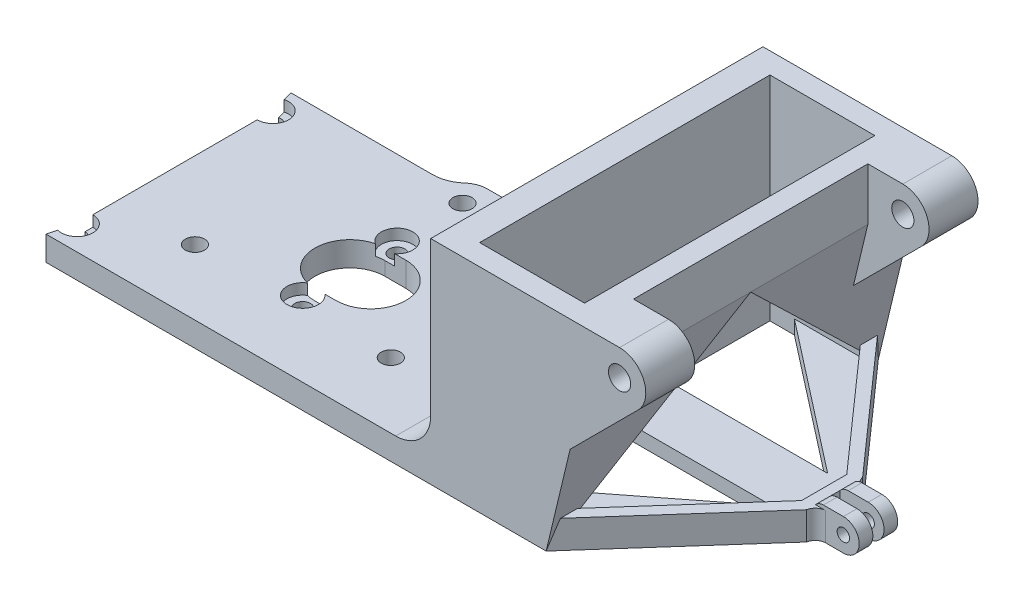
SolidWorks part; units mm, degrees
ref_plane "Front Plane" through (0, 0, 0) normal (0, 0, 1) x (1, 0, 0)
ref_plane "Top Plane" through (0, 0, 0) normal (0, 1, 0) x (1, 0, 0)
ref_plane "Right Plane" through (0, 0, 0) normal (1, 0, 0) x (0, 0, -1)
sketch "Sketch1" plane through (0, 0, 0) normal (0, 1, 0) x (1, 0, 0)
  line L1 (-35, 60) -> (80, 60)
  line L2 (-35, 60) -> (-35, -35)
  line L3 (-35, -35) -> (80, -35)
  line L4 (80, 60) -> (80, -35)
  point P0 (0, 0)
  dimension "D1" = 115
  dimension "D2" = 95
  dimension "D3" = 35
  dimension "D4" = 35
extrude "Extrude1" add sketch "Sketch1" along normal blind 7
sketch "Sketch2" plane through (0, 0, 0) normal (0, 1, 0) x (1, 0, 0)
  line L0 (-28.109, -30.4503) -> (-28.109, 28) construction
  line L1 (-35, 60) -> (-35, -35) construction
  line L2 (-47.7977, 0) -> (51.3963, 0) construction
  line L3 (21.891, -18.2702) -> (21.891, 18.8238) construction
  line L4 (5, -25.5364) -> (5, 23.1606) construction
  line L5 (-13, -30.4503) -> (-13, 32.9416) construction
  line L6 (38.782, 10.2941) -> (38.782, -21.3756) construction
  line L7 (20.5161, -20) -> (37.327, -20) construction
  line L8 (21.891, -13.5) -> (-7.9984, -13.5) construction
  line L9 (21.891, 10) -> (27.891, 10)
  line L10 (21.891, -10) -> (27.891, -10)
  circle A0 centre (-6.109, -16.3) radius 2.75
  circle A1 centre (49.891, -16.3) radius 2.75
  circle A2 centre (-28.109, -28) radius 2.25
  circle A3 centre (-28.109, 28) radius 2.25
  circle A4 centre (21.891, 32.2) radius 2.75
  arc A5 (21.891, 10) -> (21.891, -10) centre (21.891, 0) ccw
  circle A6 centre (21.891, -13.5) radius 2.25
  circle A7 centre (21.891, 13.5) radius 2.25
  arc A8 (27.891, 10) -> (27.891, -10) centre (27.891, 0) cw
  dimension "D4" = 16.891
  dimension "D5" = 28
  dimension "D6" = 4.5
  dimension "D7" = 50
  dimension "D10" = 28
  dimension "D11" = 2.8
  dimension "D12" = 4.5
  dimension "D13" = 4.5
  dimension "D17" = 48.5
  dimension "D18" = 5.5
  dimension "D19" = 5.5
  dimension "D21" = 10
  dimension "D23" = 6
  dimension "D3" = 4.5
  dimension "D14" = 5.5
  dimension "D16" = 28
  dimension "D1" = 6.891
  dimension "D2" = 28
  dimension "D8" = 13.5
  dimension "D9" = 13.5
  dimension "D15" = 40
  dimension "D20" = 18
extrude "Extrude7" cut sketch "Sketch2" along normal blind 7
hole_wizard "CBORE for M4 Pan Head Machine Screw2" positions "3DSketch10" profile "Sketch14" counterbore size "M4" standard "Ansi Metric" end condition through all
sketch3d "3DSketch10"
  line L0 (-28.109, 7, -28) -> (-28.109, 0, -28) construction
  line L1 (21.891, 7, -13.5) -> (21.891, 0, -13.5) construction
  line L2 (21.891, 7, 13.5) -> (21.891, 0, 13.5) construction
  line L3 (-28.109, 7, 28) -> (-28.109, 0, 28) construction
  point P0 (-28.109, 7, -28)
  point P4 (21.891, 7, -13.5)
  point P8 (21.891, 7, 13.5)
  point P12 (-28.109, 7, 28)
sketch "Sketch14" plane through (-28.109, 7, -28) normal (1, 0, 0) x (0, 0, 1)
  line L0 (0, 0) -> (0, 7)
  line L1 (0, 7) -> (2.25, 7)
  line L3 (2.25, 7) -> (2.25, 3.1)
  line L4 (2.25, 3.1) -> (4.5, 3.1)
  line L5 (4.5, 3.1) -> (4.5, 0)
  line L7 (4.5, 0) -> (0, 0)
  line L11 (0, -6.35) -> (0, 107.95) construction
  dimension "Thru Hole Dia." = 4.5
  dimension "Thru Hole Depth" = 7
  dimension "C'Bore Dia." = 9
  dimension "C'Bore Depth" = 3.1
sketch "Sketch18" plane through (0, 7, 0) normal (0, 1, 0) x (1, 0, 0)
  line L0 (26.1303, 32.2) -> (16.7823, 32.2) construction
  line L1 (21.891, 39.3001) -> (21.891, 26.9019) construction
  line L2 (30, 39.3001) -> (21.891, 39.3001)
  line L4 (-30, -35) -> (-35, -35)
  line L5 (-35, 60) -> (-35, -35) construction
  line L6 (-35, 35) -> (-35, 60)
  line L7 (-35, 60) -> (80, 60)
  line L8 (80, 60) -> (80, 39.3001)
  line L9 (-28.109, 28) -> (-28.109, -28)
  line L10 (-28.109, -28) -> (-30, -35)
  line L11 (-35, -35) -> (80, -35) construction
  line L12 (-30, 35) -> (15.4327, 35)
  line L13 (-35, -35) -> (-35, 35)
  line L14 (-28.109, 28) -> (-30, 35)
  line L15 (35, 44.3001) -> (35, 60)
  arc A0 (21.891, 39.3001) -> (15.4327, 35) centre (21.891, 32.3001) ccw
  arc A1 (35, 44.3001) -> (30, 39.3001) centre (30, 44.3001) cw
  circle M1 centre (-28.109, 28) radius 4.5
  circle M4 centre (-28.109, -28) radius 4.5
  line M8 (-35, 60) -> (-35, -35)
  line M9 (-35, -35) -> (80, -35)
  dimension "D1" = 7
  dimension "D4" = 5
  dimension "D2" = 45
  dimension "D3" = 5
extrude "Extrude9" cut sketch "Sketch18" against normal through all contours A1 L15 L7 L10 L9 L14 L12 A0 L2 M8 M9 M4 M1 | L9 L14 M1 | L10 L9 M4 region at (-7.338, 7, -38.5155) region at (-30.1578, 7, -27.7281) region at (-30.1578, 7, 27.7281)
fillet "Fillet1" radius 10 2 edges at (35, 3.5, -60) (15.4327, 3.5, -35)
sketch "Sketch19" plane through (80, 0, 0) normal (1, 0, 0) x (0, 0, -1)
  line L0 (-35, 7) -> (-35, 0) construction
  line L1 (60, 0) -> (-35, 0)
  line L2 (60, 0) -> (60, 60.9)
  line L3 (60, 60.9) -> (-35, 60.9)
  line L4 (-35, 0) -> (-35, 60.9)
  dimension "D1" = 60.9
extrude "Boss-Extrude1" add sketch "Sketch19" along normal blind 8
sketch "Sketch20" plane through (0, 0, -60) normal (0, 0, -1) x (-1, 0, 0)
  line L0 (-88, 0) -> (-113, 0)
  line L1 (-113, 0) -> (-124, 45.9)
  line L2 (-124, 45.9) -> (-124, 60.9)
  line L3 (-124, 60.9) -> (-88, 60.9)
  line L10 (-88, 0) -> (-45, 0)
  line L11 (-45, 0) -> (-45, 7)
  line L12 (-45, 7) -> (-80, 7)
  line L13 (-80, 7) -> (-80, 60.9)
  line L14 (-80, 60.9) -> (-88, 60.9)
  line L15 (-88, 60.9) -> (-88, 0)
  line L16 (-88, 0) -> (-45, 0)
  line L17 (-45, 0) -> (-45, 7)
  line L18 (-45, 7) -> (-80, 7)
  line L19 (-80, 7) -> (-80, 60.9)
  line L20 (-80, 60.9) -> (-88, 60.9)
  dimension "D1" = 15
  dimension "D2" = 36
  dimension "D3" = 25
  dimension "D4" = 0
extrude "Boss-Extrude2" add sketch "Sketch20" against normal blind 6
sketch "Sketch21" plane through (0, 0, 35) normal (0, 0, 1) x (1, 0, 0)
  line L5 (88, 60.9) -> (88, 0)
  line L6 (88, 0) -> (113, 0)
  line L7 (113, 0) -> (124, 45.9)
  line L8 (124, 45.9) -> (124, 60.9)
  line L9 (124, 60.9) -> (88, 60.9)
  line L10 (88, 60.9) -> (88, 0)
  line L11 (88, 0) -> (113, 0)
  line L12 (113, 0) -> (124, 45.9)
  line L13 (124, 45.9) -> (124, 60.9)
  line L14 (124, 60.9) -> (88, 60.9)
  dimension "D1" = 0
extrude "Boss-Extrude3" add sketch "Sketch21" against normal blind 6
sketch "Sketch22" plane through (0, 0, -54) normal (0, 0, 1) x (1, 0, 0)
  line L0 (88, 60.9) -> (124, 60.9) construction
  line L1 (124, 45.9) -> (118, 45.9)
  line L2 (124, 45.9) -> (124, 60.9)
  line L3 (124, 60.9) -> (118, 60.9)
  line L4 (118, 45.9) -> (118, 60.9)
  dimension "D1" = 6
extrude "Boss-Extrude4" add sketch "Sketch22" along normal up to surface (83 mm away) up to face at (107.4, 33.54, 29)
sketch "Sketch23" plane through (106.8626, -25.6098, 0) normal (0.9725, -0.2331, 0) x (0, 0, -1)
  line L0 (54, 32.0346) -> (12.5, 73.5346)
  line L1 (54, 73.5346) -> (54, 26.3349) construction
  line L2 (-29, 73.5346) -> (54, 73.5346) construction
  line L3 (12.5, 73.5346) -> (-29, 32.0346)
  line L4 (-29, 26.3349) -> (-29, 73.5346) construction
  line L5 (-29, 26.3349) -> (-29, 73.5346)
  line L6 (-29, 73.5346) -> (54, 73.5346)
  line L7 (54, 73.5346) -> (54, 26.3349)
  line M4 (54, 73.5346) -> (54, 26.3349)
  dimension "D1" = 45
extrude "Boss-Extrude5" add sketch "Sketch23" against normal up to vertex (5.8348 mm away) contours L6 L0 M4 | L6 L5 L3 region at (120.7761, 32.4476, 15.1667) region at (120.7761, 32.4476, -40.1667) up to point (118, 45.9, 29)
sketch "Sketch25" plane through (0, 0, -60) normal (0, 0, -1) x (-1, 0, 0)
  line L0 (-124, 60.9) -> (-80, 60.9) construction
  line L1 (-124, 45.9) -> (-134, 45.9)
  line L2 (-124, 45.9) -> (-124, 60.9)
  line L3 (-124, 60.9) -> (-134, 60.9)
  line L4 (-139.3033, 48.0967) -> (-119.869, 28.6624)
  line L5 (-124, 45.9) -> (-113, 0) construction
  line L6 (-119.869, 28.6624) -> (-124, 45.9)
  line L7 (-113, 0) -> (-45, 0) construction
  arc A0 (-134, 60.9) -> (-134, 45.9) centre (-134, 53.4) ccw
  circle A1 centre (-134, 53.4) radius 3.175
  line M8 (-124, 60.9) -> (-124, 45.9)
  line M9 (-124, 45.9) -> (-113, 0)
  dimension "D2" = 6.35
  dimension "D1" = 10
  dimension "D3" = 45
extrude "Boss-Extrude6" add sketch "Sketch25" against normal blind 14 contours L3 A0 L1 A1 M8 | A0 L4 L1 M9 region at (127.0971, 40.2198, -60) region at (129, 46.1305, -60)
sketch "Sketch26" plane through (0, 0, 35) normal (0, 0, 1) x (1, 0, 0)
  line L4 (134, 60.9) -> (124, 60.9)
  line L5 (124, 60.9) -> (124, 45.9)
  line L6 (124, 45.9) -> (119.869, 28.6624)
  line L7 (119.869, 28.6624) -> (139.3033, 48.0967)
  line L8 (134, 60.9) -> (124, 60.9)
  line L9 (124, 60.9) -> (124, 45.9)
  line L10 (124, 45.9) -> (119.869, 28.6624)
  line L11 (119.869, 28.6624) -> (139.3033, 48.0967)
  circle A0 centre (134, 53.4) radius 3.175 construction
  arc A1 (139.3033, 48.0967) -> (134, 60.9) centre (134, 53.4) ccw
  arc A2 (139.3033, 48.0967) -> (134, 60.9) centre (134, 53.4) ccw
  circle A3 centre (134, 53.4) radius 3.175
  dimension "D1" = 0
extrude "Boss-Extrude7" add sketch "Sketch26" against normal blind 14
fillet "Fillet2" radius 10 1 edges at (80, 7, -12.5)
sketch "Sketch27" plane through (0, 0, 0) normal (0, -1, 0) x (1, 0, 0)
  line L0 (113, 29) -> (113, 35) construction
  line L1 (88, -4.5) -> (148, -4.5)
  line L2 (88, -4.5) -> (88, -20.5)
  line L3 (88, -20.5) -> (148, -20.5)
  line L4 (148, -4.5) -> (148, -20.5)
  line L5 (113, -54) -> (113, -60) construction
  line L6 (88, 29) -> (88, -54) construction
  line L7 (113, -60) -> (45, -60) construction
  line L8 (-30, 35) -> (113, 35) construction
  line L9 (113, 29) -> (113, 35)
  line L10 (113, -54) -> (113, -60)
  line L11 (88, 29) -> (88, -54)
  line L12 (113, -60) -> (45, -60)
  line L13 (-30, 35) -> (113, 35)
  line L14 (88, -12.5) -> (148, -12.5) construction
  line L15 (113, 35) -> (148, -4.5)
  line L16 (148, -20.5) -> (113, -60)
  line L17 (138, -20.5) -> (95, -54)
  line L18 (113, -54) -> (88, -54) construction
  line L19 (138, -4.5) -> (95, 29)
  line L20 (88, 29) -> (113, 29) construction
  line L21 (88, 29) -> (113, 29)
  line L22 (113, -54) -> (88, -54)
  point P16 (0, 0)
  line M17 (113, -60) -> (113, -54)
  line M18 (113, -54) -> (88, -54)
  line M19 (88, -54) -> (88, 29)
  line M20 (88, 29) -> (113, 29)
  line M21 (113, 29) -> (113, 35)
  dimension "D1" = 60
  dimension "D2" = 16
  dimension "D3" = 7
  dimension "D4" = 7
  dimension "D5" = 10
extrude "Boss-Extrude8" add sketch "Sketch27" against normal blind 4 contours L19 L1 L15 M21 M20 | L11 L14 L4 L1 | L3 L17 L16 M18 M17 | L14 L3 L4 M19 region at (118, 0, -8.5) region at (122.196, 0, 14.9406) region at (118, 0, -16.5) region at (122.196, 0, -39.9406)
sketch "Sketch28" plane through (0, 4, 0) normal (0, 1, 0) x (1, 0, 0)
  line L0 (148, 15.5819) -> (113.9586, 54)
  line L1 (148, 4.5) -> (148, 20.5) construction
  line L2 (113.9586, -29) -> (148, 9.4181)
  line L3 (145, 23.8857) -> (145, 1.1143)
  line L14 (113.9586, 58.9181) -> (113.9586, 54)
  line L15 (113.9586, 54) -> (95, 54)
  line L16 (95, 54) -> (138, 20.5)
  line L17 (138, 20.5) -> (88, 20.5)
  line L18 (88, 20.5) -> (88, 4.5)
  line L19 (88, 4.5) -> (138, 4.5)
  line L20 (138, 4.5) -> (95, -29)
  line L21 (95, -29) -> (113.9586, -29)
  line L22 (113.9586, -29) -> (113.9586, -33.9181)
  line L23 (113.9586, -33.9181) -> (148, 4.5)
  line L24 (148, 4.5) -> (148, 20.5)
  line L25 (148, 20.5) -> (113.9586, 58.9181)
  line L26 (113.9586, 58.9181) -> (113.9586, 54)
  line L27 (113.9586, 54) -> (95, 54)
  line L28 (95, 54) -> (138, 20.5)
  line L29 (138, 20.5) -> (88, 20.5)
  line L30 (88, 20.5) -> (88, 4.5)
  line L31 (88, 4.5) -> (138, 4.5)
  line L32 (138, 4.5) -> (95, -29)
  line L33 (95, -29) -> (113.9586, -29)
  line L34 (113.9586, -29) -> (113.9586, -33.9181)
  line L35 (113.9586, -33.9181) -> (148, 4.5)
  line L36 (148, 4.5) -> (148, 20.5)
  line L37 (148, 20.5) -> (113.9586, 58.9181)
  line M15 (113.9586, 58.9181) -> (113.9586, 54)
  line M23 (113.9586, -29) -> (113.9586, -33.9181)
  line M24 (113.9586, -33.9181) -> (148, 4.5)
  line M25 (148, 4.5) -> (148, 20.5)
  line M26 (148, 20.5) -> (113.9586, 58.9181)
  dimension "D2" = 3
  dimension "D1" = 0
extrude "Boss-Extrude9" add sketch "Sketch28" along normal blind 4 contours L0 M25 M26 M15 | L2 M23 M24 M25 | L3 L0 M26 M25 | L0 L3 L2 M25 | L2 L3 M24 M25 region at (146.3227, 4, -12.5) region at (146.5, 4, -19.7338) region at (129.4793, 4, -38.9429) region at (146.5, 4, -5.2662) region at (129.4793, 4, 13.9429)
ref_plane "Plane1" through (0, 0, -12.5) normal (0, 0, 1) x (1, 0, 0)
sketch "Sketch29" plane through (0, 0, -12.5) normal (0, 0, 1) x (1, 0, 0)
  line L0 (148, 9.06) -> (148, 0)
  line L2 (148, 9.06) -> (156, 9.06)
  line L3 (148, 9.06) -> (148, 0)
  line L4 (148, 0) -> (156, 0)
  line L5 (156, 9.06) -> (156, 0) construction
  circle A0 centre (156, 4.53) radius 4.53
  circle A1 centre (156, 4.53) radius 1.778
  dimension "D3" = 3.556
  dimension "D1" = 9.06
  dimension "D2" = 8
extrude "Boss-Extrude10" add sketch "Sketch29" along normal mid plane 11 contours L5 A0 A1 | A0 L5 A1 | A0 L2 L0 L4 region at (150.3361, 4.53, -12.5) region at (158.1353, 4.53, -12.5) region at (153.8647, 4.53, -12.5)
extrude "Cut-Extrude1" cut sketch "Sketch29<3>" against normal mid plane 3.2 contours A0 L2 L0 L4 | L5 A0 A1 | A0 L5 A1 region at (150.3361, 4.53, -12.5) region at (158.1353, 4.53, -12.5) region at (153.8647, 4.53, -12.5)
sketch "Sketch29<3>" plane through (0, 0, -12.5) normal (0, 0, 1) x (1, 0, 0) same geometry as "Sketch29"
fillet "Fillet3" radius 3 4 edges at (148, 9.06, -16.05) (148, 9.06, -8.95) (148, 4, -18) (148, 4, -7)
